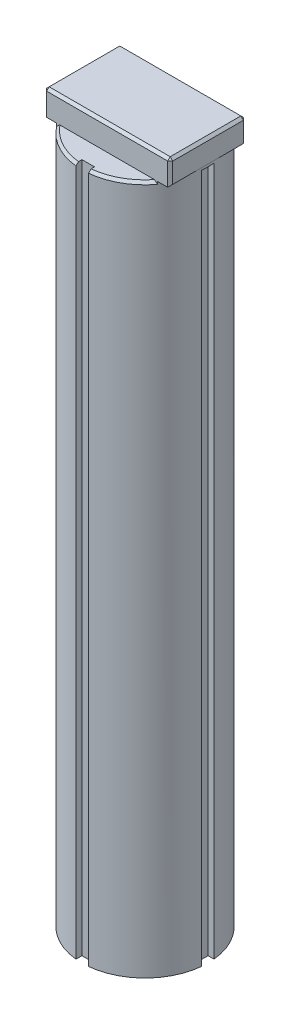
SolidWorks part; units mm, degrees
material "AISI 304"
ref_plane "Front Plane" through (0, 0, 0) normal (0, 0, 1) x (1, 0, 0)
ref_plane "Top Plane" through (0, 0, 0) normal (0, 1, 0) x (1, 0, 0)
ref_plane "Right Plane" through (0, 0, 0) normal (1, 0, 0) x (0, 0, -1)
sketch "Sketch1" plane through (0, 0, 0) normal (0, 1, 0) x (1, 0, 0)
  circle A0 centre (0, 0) radius 75
  dimension "D1" = 150
extrude "Boss-Extrude1" add sketch "Sketch1" along normal blind 820
sketch "Sketch2" plane through (0, 0, 0) normal (0, 0, 1) x (1, 0, 0)
  line L1 (-75, 850) -> (75, 850)
  line L2 (-75, 850) -> (-75, 820)
  line L3 (-75, 820) -> (75, 820)
  line L4 (75, 850) -> (75, 820)
  line L5 (-75, 850) -> (75, 820) construction
  line L6 (-75, 820) -> (75, 850) construction
  point P0 (0, 835)
  dimension "D1" = 820
  dimension "D2" = 150
  dimension "D3" = 30
extrude "Boss-Extrude2" add sketch "Sketch2" along normal blind 90 from offset 45 offset against normal yes
chamfer "Chamfer1" distance 3 angle 45 2 edges at (0, 820, 75) (0, 820, -75)
chamfer "Chamfer2" distance 3 angle 45 12 edges at (75, 820, -22.5) (75, 820, 22.5) (75, 835, 45) (75, 835, -45) (-75, 835, 45) (-75, 820, 22.5) (-75, 820, -22.5) (-75, 835, -45) (75, 850, 0) (0, 850, 45) (-75, 850, 0) (0, 850, -45)
sketch "Sketch3" plane through (0, 0, 0) normal (0, -1, 0) x (1, 0, 0)
  line L0 (82.5, -7.5) -> (67.5, -7.5)
  line L1 (-7.5, 82.5) -> (7.5, 82.5)
  line L2 (-7.5, 82.5) -> (-7.5, 67.5)
  line L3 (-7.5, 67.5) -> (7.5, 67.5)
  line L4 (7.5, 82.5) -> (7.5, 67.5)
  line L5 (-7.5, 82.5) -> (7.5, 67.5) construction
  line L6 (-7.5, 67.5) -> (7.5, 82.5) construction
  line L7 (67.5, 7.5) -> (82.5, -7.5) construction
  line L8 (82.5, 7.5) -> (67.5, -7.5) construction
  line L9 (82.5, 7.5) -> (67.5, 7.5)
  line L10 (67.5, 7.5) -> (67.5, -7.5)
  line L11 (82.5, 7.5) -> (82.5, -7.5)
  line L12 (-7.5, -82.5) -> (-7.5, -67.5)
  line L13 (7.5, -67.5) -> (-7.5, -82.5) construction
  line L14 (7.5, -82.5) -> (-7.5, -67.5) construction
  line L15 (7.5, -82.5) -> (7.5, -67.5)
  line L16 (7.5, -67.5) -> (-7.5, -67.5)
  line L17 (7.5, -82.5) -> (-7.5, -82.5)
  line L18 (-82.5, 7.5) -> (-67.5, 7.5)
  line L19 (-67.5, -7.5) -> (-82.5, 7.5) construction
  line L20 (-82.5, -7.5) -> (-67.5, 7.5) construction
  line L21 (-82.5, -7.5) -> (-67.5, -7.5)
  line L22 (-67.5, -7.5) -> (-67.5, 7.5)
  line L23 (-82.5, -7.5) -> (-82.5, 7.5)
  circle A0 centre (0, 0) radius 75 construction
  point P0 (0, 75)
  dimension "D1" = 15
  dimension "D2" = 15
  dimension "D4" = 75
  dimension "D5" = 75
  dimension "D3" = 4
extrude "Cut-Extrude1" cut sketch "Sketch3" against normal up to surface (820 mm away) up to face at (-68.3607, 820, 37.1803)
ref_axis "Axis1" through (0, 817, 0) along (0, -1, 0)
